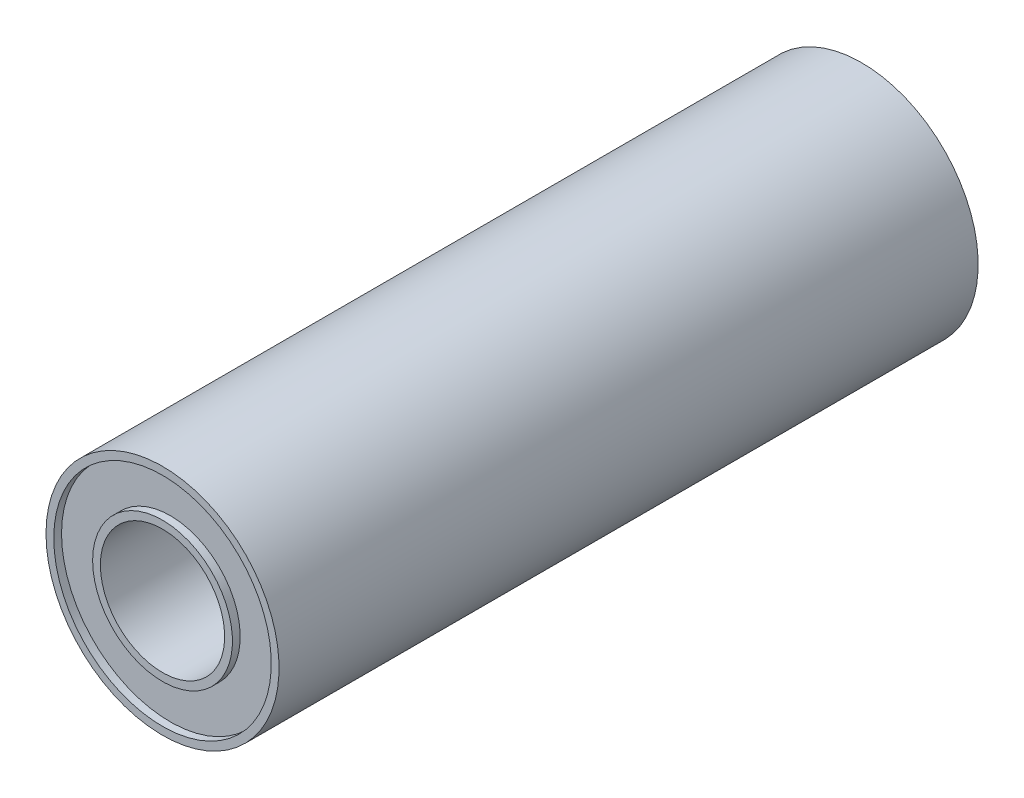
SolidWorks part; units mm, degrees
ref_plane "前视基准面" through (0, 0, 0) normal (0, 0, 1) x (1, 0, 0)
ref_plane "上视基准面" through (0, 0, 0) normal (0, 1, 0) x (1, 0, 0)
ref_plane "右视基准面" through (0, 0, 0) normal (1, 0, 0) x (0, 0, -1)
sketch "草图1" plane through (0, 0, 0) normal (0, 0, 1) x (1, 0, 0)
  circle A0 centre (0, 0) radius 4
  circle A1 centre (0, 0) radius 7.5
  circle A2 centre (0, 0) radius 7
  circle A3 centre (0, 0) radius 4.5
extrude "凸台-拉伸2" add sketch "草图1" along normal mid plane 45 contours A1 A2 | A3 A0 region at (-7.2879, 0, 0) region at (-4.3727, 0, 0)
extrude "凸台-拉伸3" add sketch "草图1<5>" along normal mid plane 44 contours A2 A3 region at (-6.802, 0, 0)
sketch "草图1<5>" plane through (0, 0, 0) normal (0, 0, 1) x (1, 0, 0) same geometry as "草图1"
